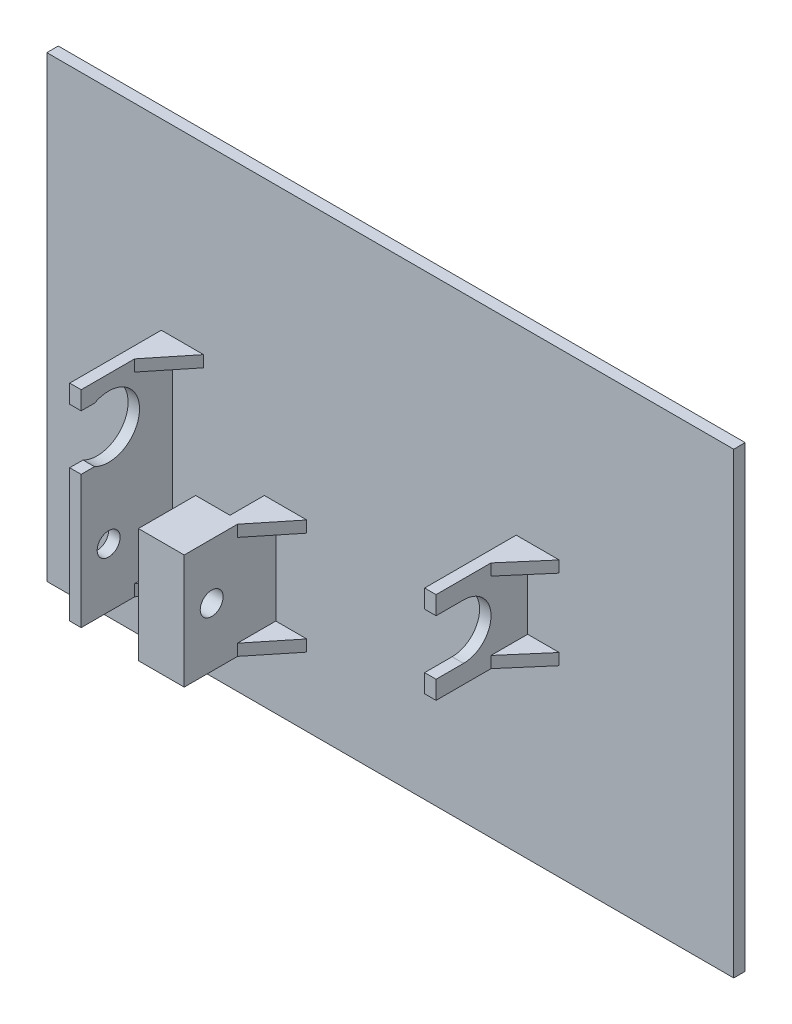
SolidWorks part; units mm, degrees
ref_plane "Front Plane" through (0, 0, 0) normal (0, 0, 1) x (1, 0, 0)
ref_plane "Top Plane" through (0, 0, 0) normal (0, 1, 0) x (1, 0, 0)
ref_plane "Right Plane" through (0, 0, 0) normal (1, 0, 0) x (0, 0, -1)
sketch "Sketch1" plane through (0, 0, 0) normal (0, 0, 1) x (1, 0, 0)
  line L1 (-150, 100) -> (150, 100)
  line L2 (-150, 100) -> (-150, -100)
  line L3 (-150, -100) -> (150, -100)
  line L4 (150, 100) -> (150, -100)
  line L5 (-150, 100) -> (150, -100) construction
  line L6 (-150, -100) -> (150, 100) construction
  point P0 (0, 0)
  dimension "D1" = 300
  dimension "D2" = 200
extrude "Boss-Extrude1" add sketch "Sketch1" along normal blind 5
sketch "Sketch3" plane through (0, 0, 5) normal (0, 0, 1) x (1, 0, 0)
  line L1 (-150, -100) -> (-130, -100)
  line L2 (-150, -100) -> (-150, -80)
  line L3 (-150, -80) -> (-130, -80)
  line L4 (-130, -100) -> (-130, -80)
  line L5 (-150, 100) -> (-130, 100)
  line L6 (-150, 100) -> (-150, 60)
  line L7 (-150, 60) -> (-130, 60)
  line L8 (-130, 100) -> (-130, 60)
  line L9 (150, 100) -> (130, 100)
  line L10 (150, 100) -> (150, 60)
  line L11 (150, 60) -> (130, 60)
  line L12 (130, 100) -> (130, 60)
  line L13 (150, -100) -> (130, -100)
  line L14 (150, -100) -> (150, -80)
  line L15 (150, -80) -> (130, -80)
  line L16 (130, -100) -> (130, -80)
  dimension "D1" = 20
  dimension "D2" = 20
  dimension "D3" = 40
extrude "Cut-Extrude1" cut sketch "Sketch3" against normal blind 5
sketch "Sketch4" plane through (0, 0, 0) normal (0, 0, -1) x (-1, 0, 0)
  line L0 (-150, -80) -> (-150, 60) construction
  line L1 (-130, -100) -> (-150, -100)
  line L2 (-130, -100) -> (-130, -60)
  line L3 (-130, -60) -> (-150, -60)
  line L4 (-150, -100) -> (-150, -60)
  line L5 (150, 60) -> (150, -80) construction
  line L6 (130, -100) -> (150, -100)
  line L7 (130, -100) -> (130, -60)
  line L8 (130, -60) -> (150, -60)
  line L9 (150, -100) -> (150, -60)
  dimension "D1" = 40
  dimension "D2" = 40
extrude "Cut-Extrude2" cut sketch "Sketch4" against normal blind 10
sketch "Sketch6" plane through (0, 0, 0) normal (0, 0, -1) x (-1, 0, 0)
  line L0 (150, 60) -> (150, -60) construction
  line L1 (-150, 100) -> (150, 100)
  line L2 (-150, 100) -> (-150, -100)
  line L3 (-150, -100) -> (150, -100)
  line L4 (150, 100) -> (150, -100)
  line L5 (130, -100) -> (-130, -100) construction
  line L6 (-130, 100) -> (130, 100) construction
  line L7 (-150, -60) -> (-150, 60) construction
extrude "Boss-Extrude2" add sketch "Sketch6" against normal blind 5
sketch "Sketch8" plane through (0, 0, 5) normal (0, 0, 1) x (1, 0, 0)
  line L0 (150, 100) -> (-150, 100) construction
  line L1 (-100, 20) -> (-95, 20)
  line L2 (-100, 20) -> (-100, -20)
  line L4 (-95, 20) -> (-95, -20)
  line L5 (-150, 100) -> (-150, -100) construction
  line L6 (-150, -100) -> (150, -100) construction
  line L7 (55, 20) -> (60, 20)
  line L8 (55, 20) -> (55, -20)
  line L9 (55, -20) -> (60, -20)
  line L10 (60, 20) -> (60, -20)
  line L12 (-100, -20) -> (-100, -70)
  line L13 (-100, -70) -> (-95, -70)
  line L14 (-95, -20) -> (-95, -70)
  dimension "D1" = 5
  dimension "D3" = 80
  dimension "D4" = 50
  dimension "D5" = 150
  dimension "D6" = 30
extrude "Boss-Extrude4" add sketch "Sketch8" along normal blind 40 contours L12 L13 L14 L4 L1 L2
extrude "Boss-Extrude5" add sketch "Sketch8<3>" along normal blind 40 contours L8 L9 L10 L7
sketch "Sketch8<3>" plane through (0, 0, 5) normal (0, 0, 1) x (1, 0, 0) same geometry as "Sketch8"
sketch "Sketch9" plane through (60, 0, 0) normal (1, 0, 0) x (0, 0, -1)
  line L0 (-45, 20) -> (-45, -20) construction
  line L1 (-45, 12) -> (-33, 12)
  line L2 (-45, 12) -> (-45, -12)
  line L3 (-45, -12) -> (-33, -12)
  line L5 (-45, -20) -> (-5, -20) construction
  arc A0 (-33, -12) -> (-33, 12) centre (-33, 0) ccw
  dimension "D3" = 24
  dimension "D1" = 24
  dimension "D2" = 8
extrude "Cut-Extrude3" cut sketch "Sketch9" against normal blind 236
sketch "Sketch10" plane through (-95, 0, 0) normal (1, 0, 0) x (0, 0, -1)
  circle A0 centre (-33, -44.2799) radius 5
  dimension "D1" = 10
extrude "Cut-Extrude4" cut sketch "Sketch10" against normal blind 236 contours A0
sketch "Sketch11" plane through (0, -70, 0) normal (0, -1, 0) x (1, 0, 0)
  line L0 (-95, 21.6604) -> (-81.5668, 5)
  line L1 (-95, 45) -> (-95, 5) construction
  line L2 (-150, 5) -> (150, 5) construction
  line L3 (-81.5668, 5) -> (-95, 5)
  line L4 (-95, 5) -> (-95, 21.6604)
  line L5 (60, 21.6604) -> (72.769, 5)
  line L6 (60, 45) -> (60, 5) construction
  line L7 (72.769, 5) -> (60, 5)
  line L8 (60, 5) -> (60, 21.6604)
extrude "Boss-Extrude6" add sketch "Sketch11" against normal blind 5 contours L0 L3 L4
sketch "Sketch12" plane through (0, 20, 0) normal (0, 1, 0) x (1, 0, 0)
  line L0 (-81.5668, -5) -> (-95, -21.6604)
  line L1 (-95, -21.6604) -> (-95, -5)
  line L2 (-95, -5) -> (-81.5668, -5)
  line L3 (60, -21) -> (73.767, -5)
  line L4 (150, -5) -> (-150, -5) construction
  line L5 (73.767, -5) -> (60, -5)
  line L6 (60, -5) -> (60, -21)
extrude "Boss-Extrude7" add sketch "Sketch12" against normal blind 5 contours L3 L5 L6
extrude "Boss-Extrude8" add sketch "Sketch12<3>" against normal blind 5 contours L0 L1 L2
sketch "Sketch12<3>" plane through (0, 20, 0) normal (0, 1, 0) x (1, 0, 0) same geometry as "Sketch12"
ref_plane "Plane1" through (0, 0, 0) normal (0, -1, 0) x (-1, 0, 0)
mirror "Mirror1" about plane through (0, 0, 0) normal (0, -1, 0) of "Boss-Extrude7"
ref_plane "Plane3" through (-75, 0, 0) normal (1, 0, 0) x (0, 0, -1)
mirror "Mirror3" about plane through (-75, 0, 0) normal (1, 0, 0) of "Cut-Extrude4", "Boss-Extrude4"
sketch "Sketch17" plane through (-55, 0, 0) normal (-1, 0, 0) x (0, 0, 1)
  line L0 (5, -20) -> (45, -20)
  line L1 (5, 20) -> (45, 20)
  line L2 (5, 20) -> (5, -20)
  line L4 (45, 20) -> (45, -12)
  line L5 (45, 20) -> (45, -70) construction
  line L6 (45, -20) -> (45, -12)
  dimension "D1" = 40
extrude "Cut-Extrude5" cut sketch "Sketch17" against normal blind 10
sketch "Sketch19" plane through (-55, 0, 0) normal (-1, 0, 0) x (0, 0, 1)
  line L0 (45, -70) -> (5, -70) construction
  line L1 (45, -20) -> (20, -20)
  line L2 (45, -20) -> (45, -70)
  line L3 (45, -70) -> (20, -70)
  line L4 (20, -20) -> (20, -70)
  dimension "D1" = 25
extrude "Boss-Extrude10" add sketch "Sketch19" along normal blind 15
sketch "Sketch20" plane through (0, -70, 0) normal (0, -1, 0) x (1, 0, 0)
  line L0 (-50, 21.718) -> (-36.4832, 5)
  line L1 (-50, 45) -> (-50, 5) construction
  line L2 (-36.4832, 5) -> (-50, 5)
  line L3 (-50, 5) -> (-50, 21.718)
extrude "Boss-Extrude11" add sketch "Sketch20" against normal blind 5
ref_plane "Plane4" through (0, -45, 0) normal (0, 1, 0) x (1, 0, 0)
mirror "Mirror4" about plane through (0, -45, 0) normal (0, 1, 0) of "Boss-Extrude11"
sketch "Sketch22" plane through (-75, 0, 0) normal (1, 0, 0) x (0, 0, -1)
  circle A0 centre (-33, -44.2799) radius 5
extrude "Cut-Extrude6" cut sketch "Sketch22" along normal blind 39
sketch "Sketch23" plane through (-100, 0, 0) normal (-1, 0, 0) x (0, 0, 1)
  circle A0 centre (33, 0) radius 13.5
  dimension "D1" = 27
extrude "Cut-Extrude7" cut sketch "Sketch23" against normal blind 10
